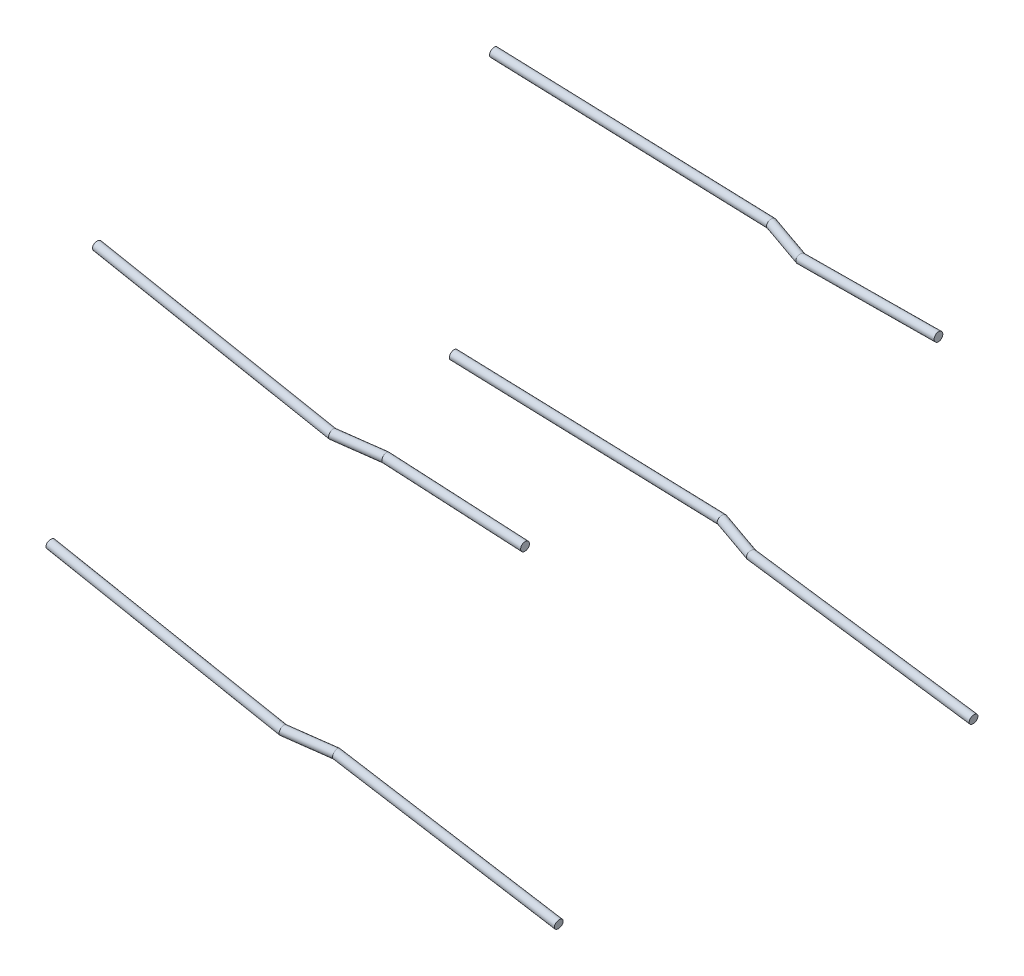
SolidWorks part; units mm, degrees
ref_plane "前视基准面" through (0, 0, 0) normal (0, 0, 1) x (1, 0, 0)
ref_plane "上视基准面" through (0, 0, 0) normal (0, 1, 0) x (1, 0, 0)
ref_plane "右视基准面" through (0, 0, 0) normal (1, 0, 0) x (0, 0, -1)
sketch3d "3D草图1"
  line L0 (50.0941, 31.0222, 38.5675) -> (78.8959, 28.0047, 36.5474)
  line L1 (78.8959, 28.0047, 36.5474) -> (83.6759, 27.6208, 37.9632)
  line L2 (52.1711, 60.8427, 36.0327) -> (82.0318, 57.7331, 34.0204)
  line L3 (82.0318, 57.7331, 34.0204) -> (86.8118, 57.3493, 35.4362)
  line L4 (52.5297, 64.7096, 81.8699) -> (82.0318, 62.0135, 84.3757)
  line L5 (82.0318, 62.0135, 84.3757) -> (86.8118, 61.3961, 83.045)
  line L6 (49.7355, 34.9474, 84.3997) -> (78.8959, 32.285, 86.9027)
  line L7 (78.8959, 32.285, 86.9027) -> (83.6759, 31.6677, 85.572)
  line L10 (109.3554, 24.2132, 38.1557) -> (83.6759, 27.6208, 37.9632)
  line L11 (83.6759, 31.6677, 85.572) -> (109.5592, 27.8433, 85.9437)
  line L12 (86.8118, 57.3493, 35.4362) -> (102.4814, 57.3493, 35.3078)
  line L13 (86.8118, 61.3961, 83.045) -> (103.0006, 60.7524, 83.2546)
  point P46 (103.3953, 61.6194, 83.686)
  point P49 (103.0821, 61.0764, 83.4136)
  point P50 (103.0006, 60.7524, 83.2546)
sweep "扫描1" add path "3D草图1" circular profile diameter 1 parameters "D3"=1
sweep "扫描2" add path "3D草图1<5>" circular profile diameter 1 parameters "D3"=1
sketch3d "3D草图1<5>" same geometry as "3D草图1"
sweep "扫描3" add path "3D草图1<6>" circular profile diameter 1 parameters "D3"=1
sketch3d "3D草图1<6>" same geometry as "3D草图1"
sweep "扫描4" add path "3D草图1<7>" circular profile diameter 1 parameters "D3"=1
sketch3d "3D草图1<7>" same geometry as "3D草图1"
